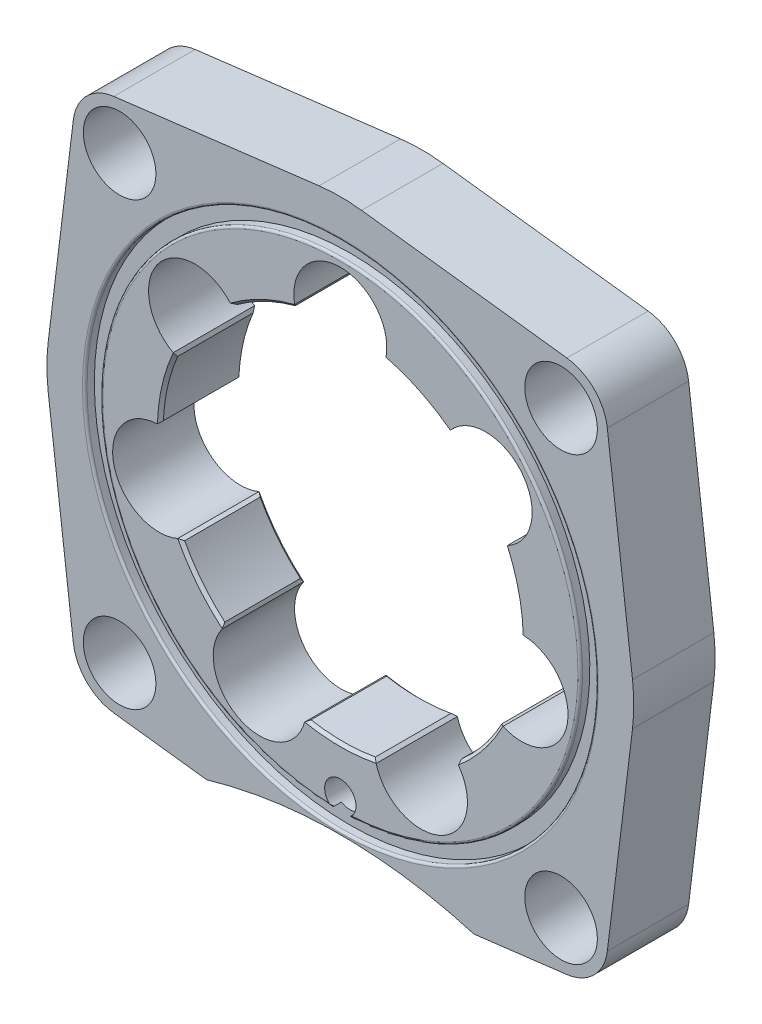
SolidWorks part; units mm, degrees
material "Black Heart Malleable Cast Iron"
ref_plane "Front Plane" through (0, 0, 0) normal (0, 0, 1) x (1, 0, 0)
ref_plane "Top Plane" through (0, 0, 0) normal (0, 1, 0) x (1, 0, 0)
ref_plane "Right Plane" through (0, 0, 0) normal (1, 0, 0) x (0, 0, -1)
sketch "Sketch1" plane through (0, 0, 0) normal (0, 0, 1) x (1, 0, 0)
  line L0 (0, 0) -> (86.0326, 0) construction
  line L1 (0, 0) -> (0, 58.9688) construction
  line L2 (0, 50.75) -> (-38.9964, 45.9618)
  line L3 (0, 50.75) -> (38.9964, 45.9618)
  line L4 (45.9618, 38.9964) -> (50.75, 0)
  line L5 (45.9618, -38.9964) -> (50.75, 0)
  line L6 (-45.9618, -38.9964) -> (-50.75, 0)
  line L7 (-45.9618, 38.9964) -> (-50.75, 0)
  line L8 (0, -50.75) -> (38.9964, -45.9618)
  line L9 (0, -50.75) -> (-38.9964, -45.9618)
  arc A0 (-45.9618, 38.9964) -> (-38.9964, 45.9618) centre (-38.0215, 38.0215) cw
  arc A1 (-38.9964, -45.9618) -> (-45.9618, -38.9964) centre (-38.0215, -38.0215) cw
  arc A2 (45.9618, -38.9964) -> (38.9964, -45.9618) centre (38.0215, -38.0215) cw
  arc A3 (38.9964, 45.9618) -> (45.9618, 38.9964) centre (38.0215, 38.0215) cw
  circle A4 centre (0, 0) radius 31
  point P14 (-45.2001, 45.2001)
  point P17 (-45.2001, -45.2001)
  point P20 (45.2001, -45.2001)
  point P23 (45.2001, 45.2001)
  dimension "D5" = 8
  dimension "D6" = 62
  dimension "D1" = 166
  dimension "D2" = 166
  dimension "D3" = 101.5
  dimension "D4" = 101.5
extrude "Extrude1" add sketch "Sketch1" along normal mid plane 14
fillet "Fillet2" radius 30 4 edges at (0, -50.75, 0) (50.75, 0, 0) (0, 50.75, 0) (-50.75, 0, 0)
chamfer "Chamfer1" distance 0.5 angle 45 2 edges at (31, 0, -7) (31, 0, 7)
hole_wizard "Ø12.5 (12.5) Diameter Hole1" positions "Sketch3" profile "Sketch2" hole size "Ø12.5" standard "Ansi Metric" end condition through all
sketch "Sketch3" plane through (0, 0, 7) normal (0, 0, 1) x (1, 0, 0)
  line L0 (0, 0) -> (0, 56.9426) construction
  line L1 (0, 0) -> (66.9225, 0) construction
  point P0 (-38, 38)
  point P1 (38, 38)
  point P3 (38, -38)
  point P5 (-38, -38)
  dimension "D1" = 76
  dimension "D2" = 76
sketch "Sketch2" plane through (-38, 38, 7) normal (1, 0, 0) x (0, -1, 0)
  line L0 (0, 0) -> (0, 14)
  line L1 (0, 14) -> (6.25, 14)
  line L2 (6.25, 14) -> (6.25, 0)
  line L5 (6.25, 0) -> (0, 0)
  line L11 (0, -6.35) -> (0, 107.95) construction
  dimension "Thru Hole Dia." = 12.5
  dimension "Thru Hole Depth" = 14
sketch "Sketch4" plane through (0, 0, 7) normal (0, 0, 1) x (1, 0, 0)
  line L2 (0, -50.75) -> (23, -47.926)
  line L3 (-23, -47.926) -> (0, -50.75)
  line L4 (0, -50.75) -> (0, 12.9408) construction
  line L5 (3.6561, -50.3011) -> (38.9964, -45.9618) construction
  line L6 (-38.9964, -45.9618) -> (-3.6561, -50.3011) construction
  arc A0 (23, -47.926) -> (-23, -47.926) centre (0, -125.789) ccw
  circle A1 centre (0, 0) radius 31 construction
  dimension "D3" = 13.6
  dimension "D1" = 46
extrude "BOTTOM CUT" cut sketch "Sketch4" against normal through all
sketch "Sketch7" plane through (0, 0, 7) normal (0, 0, 1) x (1, 0, 0)
  circle A0 centre (0, 0) radius 41.3
  circle A1 centre (0, 0) radius 44
  dimension "D1" = 82.6
  dimension "D2" = 88
extrude "O-RING CUT" cut sketch "Sketch7" against normal blind 1.65
sketch "Sketch5" plane through (0, 0, 7) normal (0, 0, 1) x (1, 0, 0)
  line L0 (0, 0) -> (0, 54.7703) construction
  line L1 (1.3999, 0) -> (33.0817, 0) construction
  circle A0 centre (0, 32) radius 8
  dimension "D1" = 16
  dimension "D2" = 80
extrude "Extrude3" cut sketch "Sketch5" against normal up to next
pattern_circular "CirPattern1" count 7 over 360 about axis through (0, 0, 7) along (0, 0, -1) of "Extrude3"
sketch "Sketch6" plane through (0, 0, 7) normal (0, 0, 1) x (1, 0, 0)
  circle A0 centre (0, -39) radius 2.7
  dimension "D1" = 5.4
  dimension "D2" = 39
extrude "PIN HOLE" cut sketch "Sketch6" against normal up to next
fillet "Fillet1" radius 0.4 2 edges at (0, 41.3, 7) (44, 0, 7)
chamfer "Chamfer2" distance 0.5 angle 45 14 edges at (-30.9876, 0.8766, 0) (-28.2992, 12.6553, 0) (-18.6351, 24.7736, 0) (-7.75, 30.0156, 0) (18.6351, 24.7736, 0) (7.75, 30.0156, 0) (30.9876, 0.8766, 0) (28.2992, 12.6553, 0) (20.0058, -23.6806, 0) (27.5385, -14.2348, 0) (6.0408, -30.4057, 0) (-6.0408, -30.4057, 0) (-20.0058, -23.6806, 0) (-27.5385, -14.2348, 0) first distance on face at (-31.8156, -7.2617, 0) first distance on face at (-25.5141, 20.3468, 0) first distance on face at (0, 32.6338, 0) first distance on face at (25.5141, 20.3468, 0) first distance on face at (31.8156, -7.2617, 0) first distance on face at (14.1593, -29.402, 0) first distance on face at (-14.1593, -29.402, 0)
sketch "Sketch8" [suppressed] plane through (0, 0, -7) normal (0, 0, -1) x (-1, 0, 0)
  line L0 (0, 0) -> (72.833, 0) construction
  line L1 (0, 0) -> (0, 53.3122) construction
  circle A0 centre (36.75, 36.75) radius 5
  circle A1 centre (36.75, -36.75) radius 5
  circle A2 centre (-36.75, -36.75) radius 5
  circle A3 centre (-36.75, 36.75) radius 5
  dimension "D1" = 73.5
  dimension "D2" = 10
  dimension "D3" = 73.5
extrude "Cut-Extrude1" [suppressed] cut sketch "Sketch8" against normal up to next
